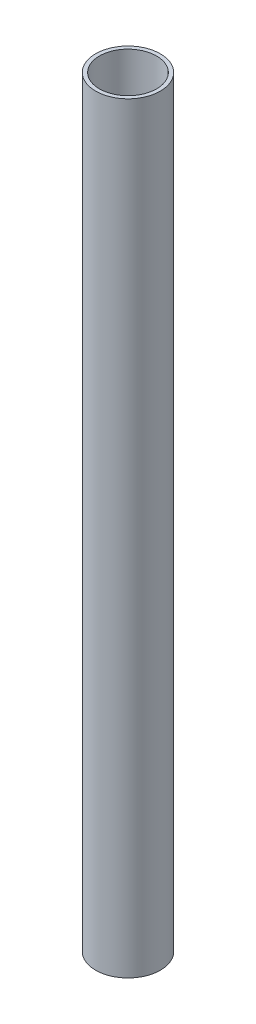
SolidWorks part; units mm, degrees
ref_plane "Спереди" through (0, 0, 0) normal (0, 0, 1) x (1, 0, 0)
ref_plane "Сверху" through (0, 0, 0) normal (0, 1, 0) x (1, 0, 0)
ref_plane "Справа" through (0, 0, 0) normal (1, 0, 0) x (0, 0, -1)
sketch "Эскиз1" plane through (0, 0, 0) normal (0, 1, 0) x (1, 0, 0)
  circle A0 centre (0, 0) radius 25.5
extrude "Вытянуть-Тонкостенный1" add sketch "Эскиз1" along normal blind 600 thin thin type one direction reverse wall 3
